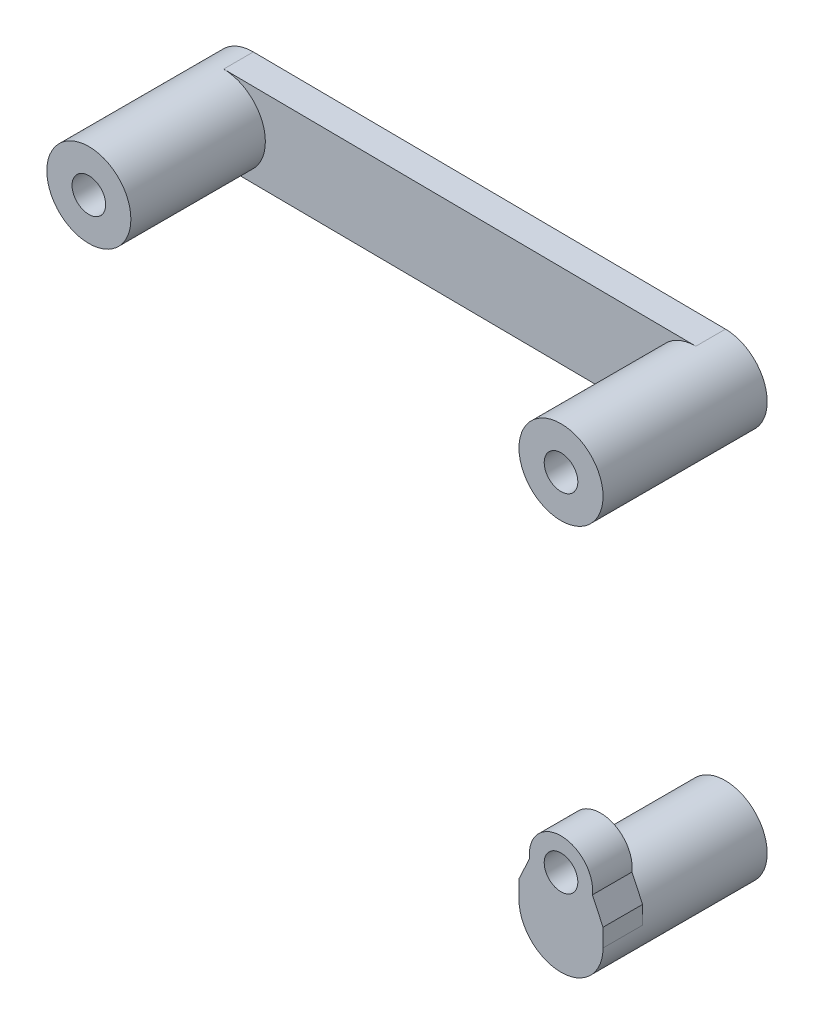
SolidWorks part; units mm, degrees
ref_plane "Ebene vorne" through (0, 0, 0) normal (0, 0, 1) x (1, 0, 0)
ref_plane "Ebene oben" through (0, 0, 0) normal (0, 1, 0) x (1, 0, 0)
ref_plane "Ebene rechts" through (0, 0, 0) normal (1, 0, 0) x (0, 0, -1)
sketch "Skizze1" plane through (0, 0, 0) normal (0, 0, 1) x (1, 0, 0)
  line L0 (94.7531, -1.5417) -> (53.3515, -1.5417) construction
  line L2 (53.6953, 39.5007) -> (53.3515, -1.5417) construction
  circle A0 centre (29.625, 16.3833) radius 4.25
  circle A1 centre (77.375, 15.9833) radius 4.25
  circle A2 centre (77.375, -19.0667) radius 4.25
  dimension "D1" = 8.5
extrude "Aufsatz-Linear austragen1" add sketch "Skizze1" along normal up to surface (16.6 mm away)
sketch "Skizze2" plane through (0, 0, 0) normal (0, 0, 1) x (1, 0, 0)
  circle A0 centre (77.375, -19.0667) radius 4.25
  circle A1 centre (77.375, -19.0667) radius 4.25 construction
extrude "Schnitt-Linear austragen1" cut sketch "Skizze2" along normal offset from surface (12.6 mm away) 4
sketch "Skizze3" plane through (0, 0, 16.6) normal (0, 0, 1) x (1, 0, 0)
  line L0 (77.375, -19.0667) -> (77.375, -23.5667) construction
  line L1 (81.625, -19.0667) -> (81.625, -23.5667)
  line L2 (73.125, -19.0667) -> (73.125, -23.5667)
  arc A0 (81.625, -19.0667) -> (73.125, -19.0667) centre (77.375, -19.0667) ccw
  arc A1 (73.125, -23.5667) -> (81.625, -23.5667) centre (77.375, -23.5667) ccw
  circle A2 centre (77.375, -19.0667) radius 4.25 construction
  point P3 (77.375, -21.3167)
  dimension "D1" = 4.5
extrude "Aufsatz-Linear austragen2" add sketch "Skizze3" against normal up to surface (4 mm away) up to face at (77.375, -14.8167, 12.6)
sketch "Skizze4" plane through (0, 0, 16.6) normal (0, 0, 1) x (1, 0, 0)
  circle A0 centre (77.375, -23.5667) radius 4.25
  arc A1 (73.125, -23.5667) -> (81.625, -23.5667) centre (77.375, -23.5667) ccw construction
extrude "Aufsatz-Linear austragen3" add sketch "Skizze4" against normal up to surface (16.6 mm away)
sketch "Skizze5" plane through (0, 0, 0) normal (0, 0, 1) x (1, 0, 0)
  line L0 (26.8978, 13.1236) -> (74.6478, -26.8264)
  line L1 (74.6478, -26.8264) -> (80.1022, -20.3071)
  line L2 (80.1022, -20.3071) -> (32.3522, 19.6429)
  line L3 (32.3522, 19.6429) -> (26.8978, 13.1236)
  circle A0 centre (29.625, 16.3833) radius 4.25 construction
  arc A1 (73.125, -23.5667) -> (81.625, -23.5667) centre (77.375, -23.5667) ccw construction
  arc A2 (81.625, -23.5667) -> (73.125, -23.5667) centre (77.375, -23.5667) ccw construction
extrude "Aufsatz-Linear austragen4" add sketch "Skizze5" along normal blind 3
sketch "Skizze6" plane through (0, 0, 0) normal (0, 0, -1) x (-1, 0, 0)
  line L0 (-81.625, 15.9833) -> (-81.625, -23.5667)
  line L1 (-81.625, -23.5667) -> (-73.125, -23.5667)
  line L2 (-73.125, -23.5667) -> (-73.125, 15.9833)
  line L3 (-73.125, 15.9833) -> (-81.625, 15.9833)
  circle A0 centre (-77.375, 15.9833) radius 4.25 construction
  arc A1 (-80.1022, -20.3071) -> (-74.6478, -26.8264) centre (-77.375, -23.5667) ccw construction
extrude "Aufsatz-Linear austragen5" add sketch "Skizze6" against normal up to surface (3 mm away) up to face at (53.5, -3.5917, 3)
sketch "Skizze7" plane through (0, 0, 0) normal (0, 0, -1) x (-1, 0, 0)
  line L0 (-77.4106, 20.2331) -> (-29.6606, 20.6331)
  line L1 (-29.6606, 20.6331) -> (-29.5894, 12.1334)
  line L2 (-29.5894, 12.1334) -> (-77.3394, 11.7334)
  line L3 (-77.3394, 11.7334) -> (-77.4106, 20.2331)
  arc A0 (-73.125, 15.9833) -> (-81.625, 15.9833) centre (-77.375, 15.9833) ccw construction
  arc A1 (-26.8978, 13.1236) -> (-32.3522, 19.6429) centre (-29.625, 16.3833) ccw construction
extrude "Aufsatz-Linear austragen6" add sketch "Skizze7" against normal up to surface (3 mm away) up to face at (63.4424, -0.2324, 3)
sketch "Skizze8" plane through (0, 0, 16.6) normal (0, 0, 1) x (1, 0, 0)
  line L0 (53.5686, 24.3735) -> (53.3515, -1.5417) construction
  line L1 (53.3515, -1.5417) -> (45.2408, -12.4666) construction
  circle A0 centre (29.625, 16.3833) radius 1.7
  circle A1 centre (77.375, -19.0667) radius 1.7
  circle A2 centre (77.375, 15.9833) radius 1.7
  circle A3 centre (77.375, 15.9833) radius 4.25 construction
  dimension "D1" = 3.4
extrude "Schnitt-Linear austragen2" cut sketch "Skizze8" against normal blind 4
sketch "Skizze9" plane through (0, 0, 16.6) normal (0, 0, 1) x (1, 0, 0)
  line L0 (53.556, 22.8635) -> (53.3327, -3.7917) construction
  line L1 (53.3327, -3.7917) -> (45.2259, -13.4813) construction
  circle A0 centre (29.625, 16.3833) radius 2.1
  circle A2 centre (77.375, -23.5667) radius 2.1
  circle A3 centre (77.375, 15.9833) radius 2.1
  dimension "D1" = 4.2
extrude "Schnitt-Linear austragen3" cut sketch "Skizze9" along normal blind 5.7 from surface starting at face at (62.5655, 3.111, 0)
sketch "Skizze11" plane through (0, 0, 3) normal (0, 0, 1) x (1, 0, 0)
  line L0 (26.8978, 13.1236) -> (74.6478, -26.8264)
  line L2 (73.125, 11.7687) -> (41.4465, 12.0341) construction
  line L3 (77.3394, 11.7334) -> (29.5894, 12.1334)
  line L5 (26.8978, 13.1236) -> (74.6478, -26.8264) construction
  line L6 (81.625, 15.9833) -> (81.625, -23.5667) construction
  line L7 (81.625, 15.9833) -> (81.625, -23.5667)
  arc A0 (29.5894, 12.1334) -> (26.8978, 13.1236) centre (29.625, 16.3833) cw
  arc A1 (74.6478, -26.8264) -> (81.625, -23.5667) centre (77.375, -23.5667) cw
  arc A2 (26.8978, 13.1236) -> (29.6606, 20.6331) centre (29.625, 16.3833) ccw construction
  arc A3 (78.9787, -19.6309) -> (75.7713, -19.6309) centre (77.375, -23.5667) ccw construction
  arc A4 (77.3394, 11.7334) -> (81.625, 15.9833) centre (77.375, 15.9833) ccw
  circle A5 centre (77.375, 15.9833) radius 4.25 construction
extrude "Schnitt-Linear austragen4" cut sketch "Skizze11" against normal up to surface (3 mm away) up to face at (27.525, 16.3833, 0)
sketch "Skizze12" plane through (0, 0, 16.6) normal (0, 0, 1) x (1, 0, 0)
  line L0 (73.125, -19.0667) -> (74.175, -19.0667)
  line L1 (80.575, -19.0667) -> (81.625, -19.0667)
  line L2 (73.125, -19.0667) -> (73.125, -23.5667) construction
  arc A0 (74.175, -19.0667) -> (80.575, -19.0667) centre (77.375, -19.0667) cw
  arc A1 (73.125, -19.0667) -> (81.625, -19.0667) centre (77.375, -19.0667) cw
  arc A2 (81.625, -19.0667) -> (73.125, -19.0667) centre (77.375, -19.0667) ccw construction
  circle A3 centre (77.375, -19.0667) radius 1.7 construction
  point P8 (73.9452, -21.5765)
  point P9 (73.1508, -19.5345)
  point P10 (73.125, -19.286)
  dimension "D1" = 1.5
extrude "Schnitt-Linear austragen5" cut sketch "Skizze12" against normal through all
chamfer "Fase1" distance 1.25 angle 65 2 edges at (73.125, -19.0667, 14.6) (81.625, -19.0667, 14.6) first distance on face at (73.65, -19.0667, 14.6) first distance on face at (81.1, -19.0667, 14.6)
equation "\"M2EinschmelzGewindeDurchmesser\"=3.4"
equation "\"M2EinschmelzGewindeTiefe\"= 4.0"
equation "\"M3EinschmelzGewindeDurchmesser\"= 4.2"
equation "\"M3EinschmelzGewindeTief\"= 5.7"
equation "\"M2SchraubeLoch\"=2.3"
equation "\"M3SchraubeLoch\"=3.3"
equation "\"offSetVonGummiReifen\"= 3.0"
equation "\"D1@Schnitt-Linear austragen1\"=\"M2EinschmelzGewindeTiefe\""
equation "\"D1@Skizze8\"=\"M2EinschmelzGewindeDurchmesser\""
equation "\"D1@Schnitt-Linear austragen2\"=\"M2EinschmelzGewindeTiefe\""
equation "\"D1@Skizze9\"=\"M3EinschmelzGewindeDurchmesser\""
equation "\"D1@Schnitt-Linear austragen3\"=\"M3EinschmelzGewindeTief\""
